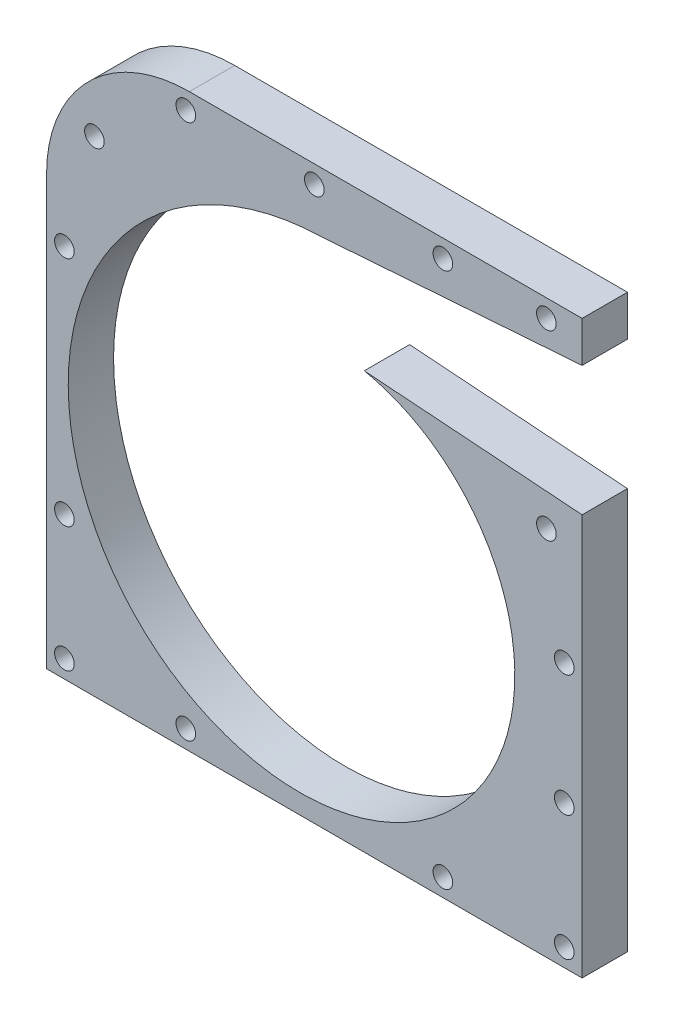
SolidWorks part; units mm, degrees
material "AISI 304"
ref_plane "Front Plane" through (0, 0, 0) normal (0, 0, 1) x (1, 0, 0)
ref_plane "Top Plane" through (0, 0, 0) normal (0, 1, 0) x (1, 0, 0)
ref_plane "Right Plane" through (0, 0, 0) normal (1, 0, 0) x (0, 0, -1)
sketch "Sketch1" plane through (0, 0, 0) normal (0, 0, 1) x (1, 0, 0)
  line L1 (-18.1818, -7.7823) -> (131.8182, -7.7823)
  line L2 (-18.1818, -7.7823) -> (-18.1818, 152.2177)
  line L3 (-18.1818, 152.2177) -> (131.8182, 152.2177)
  line L4 (131.8182, -7.7823) -> (131.8182, 152.2177)
  dimension "D1" = 160
  dimension "D2" = 150
extrude "Boss-Extrude1" add sketch "Sketch1" along normal blind 12.7
sketch "Sketch2" plane through (0, 0, 0) normal (0, 0, 1) x (1, 0, 0)
  line L0 (-18.1818, -7.7823) -> (131.8182, -7.7823) construction
  line L1 (56.8182, -7.7823) -> (56.8182, 152.2177) construction
  line L2 (131.8182, 152.2177) -> (-18.1818, 152.2177) construction
  line L3 (-18.1818, -7.7823) -> (131.8182, -7.7823) construction
  circle A0 centre (56.8182, 60.2177) radius 50 construction
  circle A1 centre (56.8182, 60.2177) radius 50
  point P0 (56.8182, 52.2686)
  dimension "D2" = 100
  dimension "D3" = 100
  dimension "D1" = 60.0509
  dimension "D4" = 68
extrude "Cut-Extrude2" cut sketch "Sketch2" along normal up to next
sketch "Sketch3" plane through (0, 0, 0) normal (0, 0, -1) x (-1, 0, 0)
  line L0 (-42.4775, -245.3976) -> (306.8559, -245.3976) construction
  line L1 (-107.6182, 60.2177) -> (-6.0182, 60.2177) construction
  circle A0 centre (-56.8182, 60.2177) radius 50.8 construction
  circle A2 centre (-56.8182, 60.2177) radius 50
  point P15 (-130.5969, 140.8094)
  dimension "D1" = 101.6
sketch "Sketch5" plane through (0, 0, 0) normal (0, 0, 1) x (1, 0, 0)
  circle A0 centre (56.8182, 60.2177) radius 50.75
  dimension "D1" = 101.5
curve "Helix/Spiral2"
sketch "Sketch8" plane through (0, 0, 12.7) normal (0, 0, 1) x (1, 0, 0)
  line L0 (58.9214, 135.5143) -> (131.8182, 140.8094)
  line L1 (131.8182, 140.8094) -> (131.8182, 104.5788)
  line L2 (131.8182, 104.5788) -> (70.8068, 109.0017)
  line L3 (131.8182, -7.7823) -> (131.8182, 152.2177) construction
  spline S0 degree 3 poles (1655.5435, -1075.034) (-228.3324, -143.7136) (-20.8405, 147.5337) (83.0512, 104.971) (85.9612, 103.445) (91.4793, 99.8417) (94.0872, 97.7644) (98.8965, 93.1188) (101.0976, 90.5506) (105.0006, 85.0032) (106.7023, 82.0242) (109.5297, 75.753) (110.6553, 72.461) (112.2729, 65.6758) (112.7649, 62.1828) (113.0797, 55.1183) (112.9026, 51.5469) (111.8674, 44.4542) (111.0093, 40.9331) (108.6254, 34.0713) (107.0996, 30.7308) (103.4181, 24.3573) (101.2626, 21.3244) (96.3841, 15.6851) (93.6612, 13.0788) (87.7328, 8.399) (84.5274, 6.3257) (77.7386, 2.801) (74.1554, 1.3498) (66.7323, -0.8617) (62.8926, -1.622) (55.0901, -2.4068) (51.1276, -2.4312) (43.2209, -1.7253) (39.277, -0.9949) (31.5517, 1.2125) (27.7706, 2.6894) (20.5125, 6.3541) (17.0358, 8.5417) (10.5204, 13.5651) (7.4819, 16.4007) (1.9637, 22.632) (-0.5158, 26.0275) (-4.8127, 33.2683) (-6.63, 37.1133) (-9.5212, 45.1235) (-10.5951, 49.2886) (-11.9436, 57.7947) (-12.2181, 62.1357) (-11.9401, 70.84) (-11.3874, 75.2031) (-9.4567, 83.7939) (-8.0786, 88.0214) (-4.5288, 96.1843) (-2.3571, 100.1197) (2.7183, 107.5494) (5.6219, 111.0435) (12.0718, 117.4547) (15.6179, 120.3715) (23.2377, 125.5099) (27.3113, 127.7313) (35.8497, 131.3839) (40.3143, 132.8149) (177.5509, 162.8074) (409.5643, -167.8845) (-1258.8776, -1322.0866) knots -1.018013 -1.018013 -1.018013 -1.018013 0.03125 0.03125 0.0625 0.0625 0.09375 0.09375 0.125 0.125 0.15625 0.15625 0.1875 0.1875 0.21875 0.21875 0.25 0.25 0.28125 0.28125 0.3125 0.3125 0.34375 0.34375 0.375 0.375 0.40625 0.40625 0.4375 0.4375 0.46875 0.46875 0.5 0.5 0.53125 0.53125 0.5625 0.5625 0.59375 0.59375 0.625 0.625 0.65625 0.65625 0.6875 0.6875 0.71875 0.71875 0.75 0.75 0.78125 0.78125 0.8125 0.8125 0.84375 0.84375 0.875 0.875 0.90625 0.90625 0.9375 0.9375 0.96875 0.96875 1.873185 1.873185 1.873185 1.873185 only from (70.8068, 109.0017) to (58.9214, 135.5143) construction
  spline S1 degree 3 poles (70.8068, 109.0017) (73.9425, 108.3689) (77.0418, 107.4329) (83.0512, 104.971) (85.9612, 103.445) (91.4793, 99.8417) (94.0872, 97.7644) (98.8965, 93.1188) (101.0976, 90.5506) (105.0006, 85.0032) (106.7023, 82.0242) (109.5297, 75.753) (110.6553, 72.461) (112.2729, 65.6758) (112.7649, 62.1828) (113.0797, 55.1183) (112.9026, 51.5469) (111.8674, 44.4542) (111.0093, 40.9331) (108.6254, 34.0713) (107.0996, 30.7308) (103.4181, 24.3573) (101.2626, 21.3244) (96.3841, 15.6851) (93.6612, 13.0788) (87.7328, 8.399) (84.5274, 6.3257) (77.7386, 2.801) (74.1554, 1.3498) (66.7323, -0.8617) (62.8926, -1.622) (55.0901, -2.4068) (51.1276, -2.4312) (43.2209, -1.7253) (39.277, -0.9949) (31.5517, 1.2125) (27.7706, 2.6894) (20.5125, 6.3541) (17.0358, 8.5417) (10.5204, 13.5651) (7.4819, 16.4007) (1.9637, 22.632) (-0.5158, 26.0275) (-4.8127, 33.2683) (-6.63, 37.1133) (-9.5212, 45.1235) (-10.5951, 49.2886) (-11.9436, 57.7947) (-12.2181, 62.1357) (-11.9401, 70.84) (-11.3874, 75.2031) (-9.4567, 83.7939) (-8.0786, 88.0214) (-4.5288, 96.1843) (-2.3571, 100.1197) (2.7183, 107.5494) (5.6219, 111.0435) (12.0718, 117.4547) (15.6179, 120.3715) (23.2377, 125.5099) (27.3113, 127.7313) (35.8497, 131.3839) (40.3143, 132.8149) (49.4812, 134.8183) (54.1832, 135.3906) (58.9214, 135.5143) knots 0 0 0 0 0.03125 0.03125 0.0625 0.0625 0.09375 0.09375 0.125 0.125 0.15625 0.15625 0.1875 0.1875 0.21875 0.21875 0.25 0.25 0.28125 0.28125 0.3125 0.3125 0.34375 0.34375 0.375 0.375 0.40625 0.40625 0.4375 0.4375 0.46875 0.46875 0.5 0.5 0.53125 0.53125 0.5625 0.5625 0.59375 0.59375 0.625 0.625 0.65625 0.65625 0.6875 0.6875 0.71875 0.71875 0.75 0.75 0.78125 0.78125 0.8125 0.8125 0.84375 0.84375 0.875 0.875 0.90625 0.90625 0.9375 0.9375 0.96875 0.96875 1 1 1 1
extrude "Cut-Extrude3" cut sketch "Sketch8" against normal up to next
fillet "Fillet1" radius 40 1 edges at (-18.1818, 152.2177, 6.35)
sketch "Sketch9" plane through (0, 0, 12.7) normal (0, 0, 1) x (1, 0, 0)
  line L0 (131.8182, 140.8094) -> (131.8182, 152.2177) construction
  line L1 (126.8182, 152.2177) -> (126.8182, -7.7823) construction
  line L2 (131.8182, 152.2177) -> (21.8182, 152.2177) construction
  line L3 (-18.1818, -7.7823) -> (131.8182, -7.7823) construction
  line L4 (131.8182, -7.7823) -> (131.8182, 104.5788) construction
  circle A1 centre (121.8182, 147.2177) radius 2.75
  circle A3 centre (92.8182, 147.2177) radius 2.75
  circle A5 centre (56.8182, 147.2177) radius 2.75
  circle A6 centre (20.8182, 147.2177) radius 2.75
  circle A7 centre (-4.7746, 128.0936) radius 2.75
  circle A8 centre (-13.1818, 97.2177) radius 2.75
  circle A9 centre (-13.1818, 32.2177) radius 2.75
  circle A10 centre (-13.1818, -2.7823) radius 2.75
  circle A11 centre (20.8182, -2.7823) radius 2.75
  circle A12 centre (92.8182, -2.7823) radius 2.75
  circle A13 centre (126.8182, -2.7823) radius 2.75
  circle A14 centre (126.8182, 32.2177) radius 2.75
  circle A15 centre (126.8182, 66.2177) radius 2.75
  circle A16 centre (121.8182, 96.2177) radius 2.75
  dimension "D11" = 10
  dimension "D2" = 29
  dimension "D3" = 36
  dimension "D4" = 31.9488
  dimension "D5" = 32
  dimension "D6" = 35
  dimension "D7" = 34
  dimension "D8" = 34
  dimension "D9" = 35
  dimension "D10" = 34
  dimension "D12" = 36
  dimension "D13" = 5
  dimension "D14" = 30
  dimension "D15" = 10
extrude "Cut-Extrude4" cut sketch "Sketch9" against normal up to next
